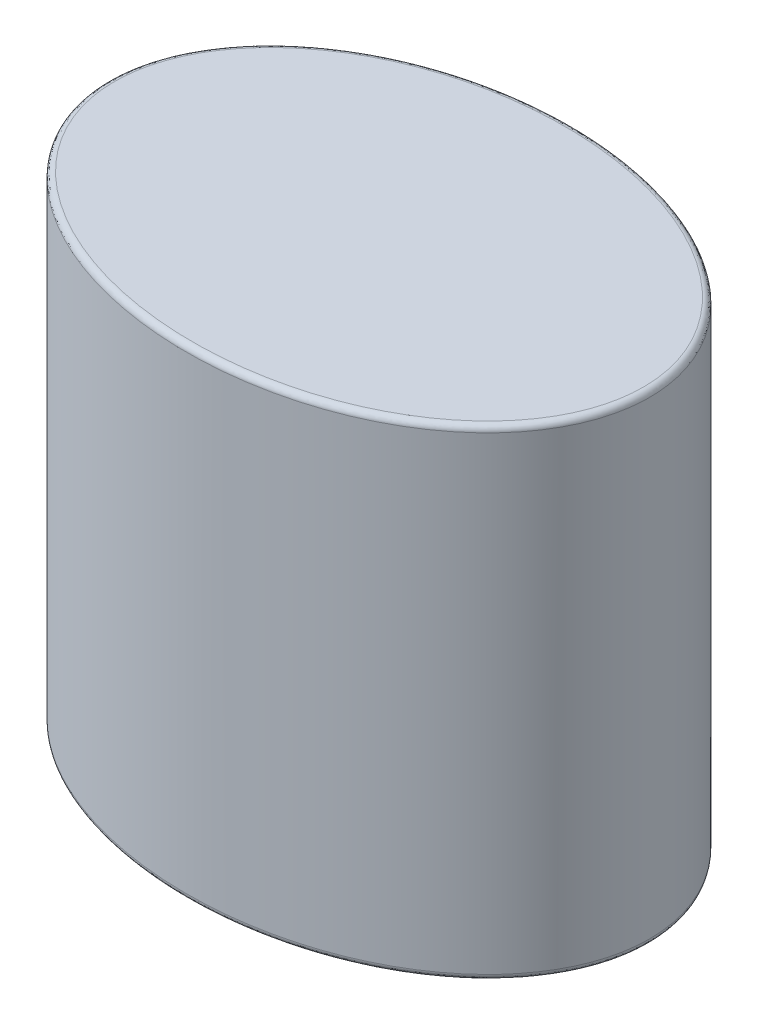
SolidWorks part; units mm, degrees
ref_plane "Front Plane" through (0, 0, 0) normal (0, 0, 1) x (1, 0, 0)
ref_plane "Top Plane" through (0, 0, 0) normal (0, 1, 0) x (1, 0, 0)
ref_plane "Right Plane" through (0, 0, 0) normal (1, 0, 0) x (0, 0, -1)
sketch "Sketch1" plane through (0, 0, 0) normal (0, 1, 0) x (1, 0, 0)
  line L0 (0, 0) -> (-35.015, 0) construction
  ellipse E0 centre (0, 0) end of major axis (-22.5, 0) minor radius 16
  dimension "D1" = 32
  dimension "D2" = 45
extrude "Boss-Extrude1" add sketch "Sketch1" along normal blind 40 contours E0
fillet "Fillet2" radius 0.5 2 edges at (-22.5, 40, 0) (-22.5, 0, 0)
